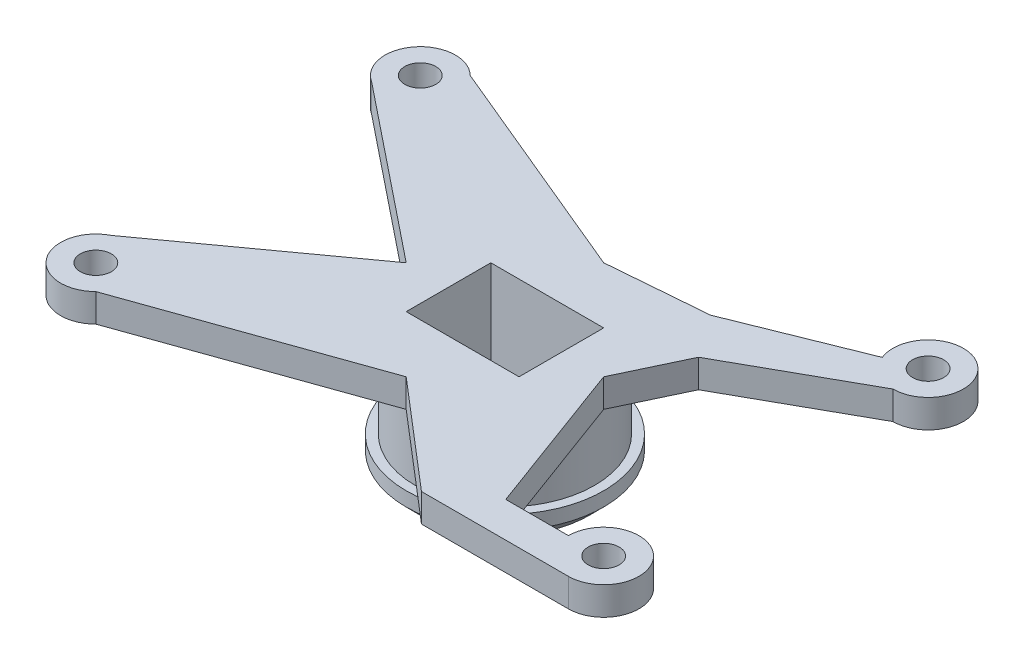
SolidWorks part; units mm, degrees
ref_plane "Front Plane" through (0, 0, 0) normal (0, 0, 1) x (1, 0, 0)
ref_plane "Top Plane" through (0, 0, 0) normal (0, 1, 0) x (1, 0, 0)
ref_plane "Right Plane" through (0, 0, 0) normal (1, 0, 0) x (0, 0, -1)
sketch "Sketch1" plane through (0, 0, 0) normal (0, 1, 0) x (1, 0, 0)
  circle A0 centre (0, 0) radius 6.35
  dimension "D1" = 12.7
extrude "Boss-Extrude1" add sketch "Sketch1" against normal blind 4
sketch "Sketch2" plane through (0, 0, 0) normal (0, 1, 0) x (1, 0, 0)
  circle A0 centre (0, 0) radius 7
  dimension "D1" = 14
extrude "Boss-Extrude2" add sketch "Sketch2" along normal blind 2
extrude "Boss-Extrude3" add sketch "Sketch2<2>" against normal blind 2 from surface starting at face at (0, -4, 6.35)
sketch "Sketch2<2>" plane through (0, 0, 0) normal (0, 1, 0) x (1, 0, 0) same geometry as "Sketch2"
chamfer "Chamfer1" distance 1 angle 45 2 edges at (0, 0, 7) (0, -6, 7)
sketch "Sketch3" plane through (0, -6, 0) normal (0, -1, 0) x (1, 0, 0)
  line L1 (-4, -3) -> (4, -3)
  line L2 (-4, -3) -> (-4, 3)
  line L3 (-4, 3) -> (4, 3)
  line L4 (4, -3) -> (4, 3)
  line L5 (-4, -3) -> (4, 3) construction
  line L6 (-4, 3) -> (4, -3) construction
  point P0 (0, 0)
  dimension "D1" = 8
  dimension "D2" = 6
extrude "Cut-Extrude1" cut sketch "Sketch3" against normal through all
sketch "Sketch4" plane through (0, 2, 0) normal (0, 1, 0) x (1, 0, 0)
  line L0 (0, 0) -> (0, 14.5) construction
  line L1 (0, 0) -> (20.3185, 0) construction
  line L2 (20.5, 14.5) -> (-20.5, 14.5)
  line L3 (-20.5, 14.5) -> (-20.5, -13.5)
  line L4 (-20.5, -13.5) -> (20.5, -13.5)
  line L5 (20.5, -13.5) -> (20.5, 14.5)
  circle A0 centre (-18, 12) radius 1.1
  circle A1 centre (-18, -11) radius 1.1
  circle A2 centre (18, -11) radius 1.1
  circle A3 centre (18, 12) radius 1.1
  point P9 (0, 14.5)
  dimension "D4" = 36
  dimension "D5" = 2.2
  dimension "D6" = 23
  dimension "D7" = 2.5
  dimension "D8" = 2.5
  dimension "D1" = 41
  dimension "D2" = 28
  dimension "D3" = 14.5
sketch "Sketch6" plane through (0, 2, 0) normal (0, 1, 0) x (1, 0, 0)
  circle A0 centre (-18, 12) radius 1.1
  circle A1 centre (18, 12) radius 1.1
  circle A2 centre (18, -11) radius 1.1
  circle A3 centre (-18, -11) radius 1.1
  circle A4 centre (-18, -11) radius 2.5
  circle A5 centre (18, -11) radius 2.5
  circle A6 centre (18, 12) radius 2.5
  circle A7 centre (-18, 12) radius 2.5
  dimension "D1" = 5
  dimension "D2" = 2.2
extrude "Boss-Extrude4" add sketch "Sketch6" along normal blind 1 and the other way blind 1 separate body
sketch "Sketch8" plane through (0, 3, 0) normal (0, 1, 0) x (1, 0, 0)
  line L0 (111.2976, -88.9946) -> (-372.7024, -88.9946) construction
sketch "Sketch7" plane through (0, 3, 0) normal (0, 1, 0) x (1, 0, 0)
  line L3 (-19.7678, 10.2322) -> (-16.2322, 10.2322)
  line L7 (-16.2322, 10.2322) -> (-16.2322, 13.7678)
  line L27 (15.5, -11) -> (11.058, -11)
  line L28 (-4, -3) -> (4, -3)
  line L29 (-4, -3) -> (-4, 3)
  line L30 (-4, 3) -> (4, 3)
  line L31 (4, -3) -> (4, 3)
  line L32 (-4, -3) -> (4, 3) construction
  line L33 (-4, 3) -> (4, -3) construction
  line L34 (11.058, -11) -> (7, 0)
  line L35 (0, 0) -> (20.3185, 0) construction
  line L36 (18, -13.5) -> (7.583, -13.5)
  line L37 (-20.5, -13.5) -> (20.5, -13.5) construction
  line L38 (7.583, -13.5) -> (0, -7)
  line L39 (-19.7678, -9.2322) -> (-16.2322, -9.2322)
  line L40 (-16.2322, -12.7678) -> (0, -7)
  line L41 (-19.7678, -9.2322) -> (-7, 0)
  line L42 (-19.7678, 10.2322) -> (-7, 0)
  line L43 (-16.2322, -9.2322) -> (-16.2322, -12.7678)
  line L44 (-16.2322, 13.7678) -> (0, 7)
  line L45 (0, 0) -> (0, 14.5) construction
  line L46 (0, 7) -> (7, 7.5722)
  line L48 (7, 0) -> (9.1598, 4.5634)
  line L51 (15.5, -11) -> (18, -13.5)
  line L52 (7, 7.5722) -> (15.6808, 11.0665)
  line L53 (15.6808, 11.0665) -> (18, 9.5)
  line L54 (18, 9.5) -> (9.1598, 4.5634)
  circle A0 centre (18, 12) radius 2.5 construction
  circle A5 centre (18, -11) radius 2.5 construction
  circle A6 centre (0, 0) radius 7 construction
  circle A7 centre (-18, -11) radius 2.5 construction
  circle A8 centre (-18, 12) radius 2.5 construction
  point P34 (0, 0)
  dimension "D2" = 60
extrude "Boss-Extrude5" add sketch "Sketch7" against normal up to surface (2 mm away) up to face at (-18, 1, -10.9)
